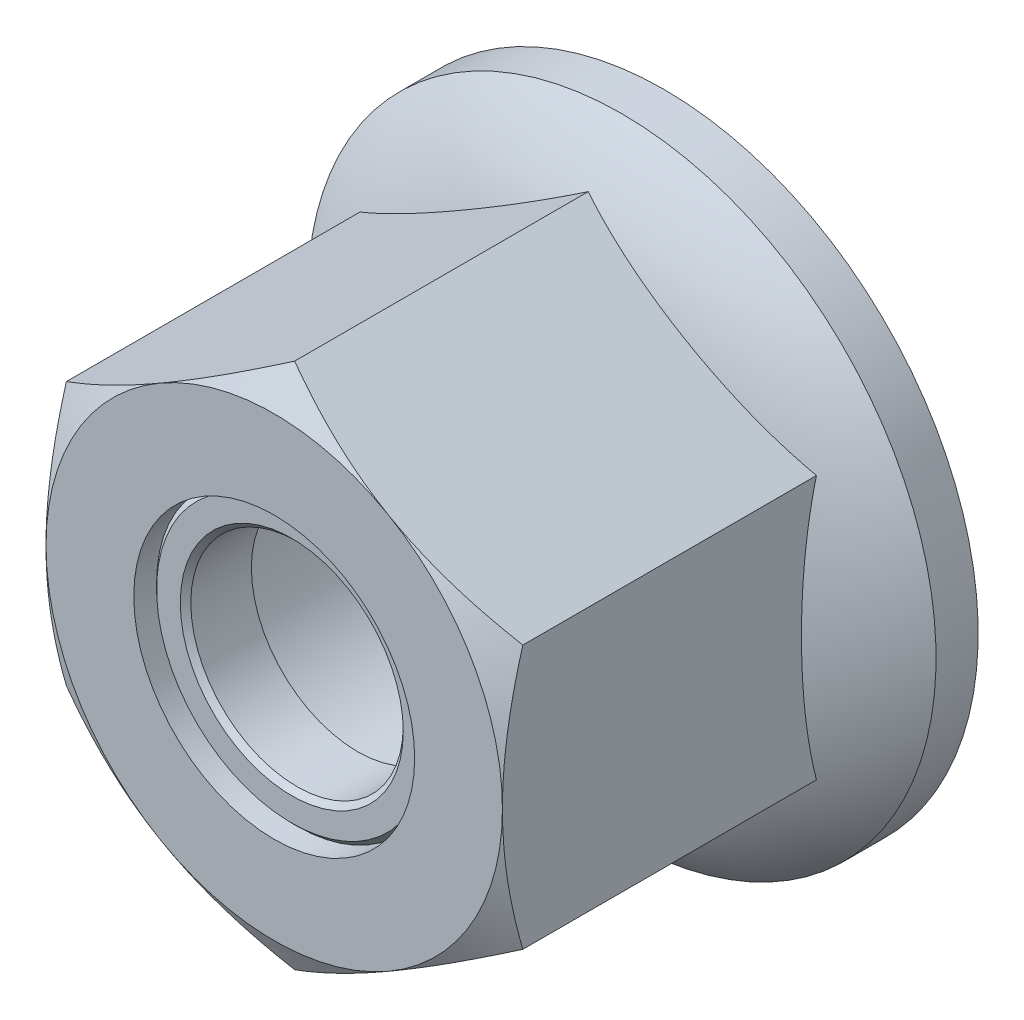
SolidWorks part; units mm, degrees
material "Alloy Steel"
ref_plane "Front Plane" through (0, 0, 0) normal (0, 0, 1) x (1, 0, 0)
ref_plane "Top Plane" through (0, 0, 0) normal (0, 1, 0) x (1, 0, 0)
ref_plane "Right Plane" through (0, 0, 0) normal (1, 0, 0) x (0, 0, -1)
sketch "Sketch1" plane through (0, 0, 0) normal (0, 0, 1) x (1, 0, 0)
  line L1 (0, 7.5056) -> (-6.5, 3.7528)
  line L2 (-6.5, 3.7528) -> (-6.5, -3.7528)
  line L3 (-6.5, -3.7528) -> (0, -7.5056)
  line L4 (0, -7.5056) -> (6.5, -3.7528)
  line L5 (6.5, -3.7528) -> (6.5, 3.7528)
  line L6 (6.5, 3.7528) -> (0, 7.5056)
  circle A0 centre (0, 0) radius 6.5 construction
  circle A1 centre (0, 0) radius 4
  dimension "Thread Size" = 8
  dimension "Hex" = 13
extrude "Extrude1" add sketch "Sketch1" against normal blind 11.1
sketch "Sketch2" plane through (0, 0, 0) normal (0, 0, 1) x (1, 0, 0)
  circle A0 centre (0, 0) radius 6.5 construction
  circle A1 centre (0, 0) radius 6.5
extrude "Cut-Extrude1" cut sketch "Sketch2" against normal through all draft 60 flip side to cut
sketch "Sketch3" plane through (0, 0, 0) normal (1, 0, 0) x (0, 0, -1)
  line L0 (11.1, 8.95) -> (11.1, 4)
  line L1 (11.1, 4) -> (8.1, 4)
  line L2 (11.1, 8.95) -> (9.9, 8.95)
  line L3 (0, 0) -> (11.1, 0) construction
  line L4 (0, -3.7528) -> (0, 3.7528) construction
  line L5 (11.1, -3.7528) -> (11.1, 3.7528) construction
  line L6 (11.1, 3.7528) -> (11.1, 7.5056) construction
  line L7 (11.1, -4) -> (11.1, 4) construction
  line L8 (8.1, 4) -> (8.1, 8.95) construction
  arc A0 (9.9, 8.95) -> (8.1, 4) centre (15.8062, 4) ccw
  dimension "Flange OD" = 17.9
  dimension "Flange Thickness" = 1.2
  dimension "D1" = 1.8
revolve "Revolve1" add sketch "Sketch3" angle 360 about L3
sketch "Sketch5" plane through (0, 0, 0) normal (0, 0, 1) x (1, 0, 0)
  circle A1 centre (0, 0) radius 4
  circle A2 centre (0, 0) radius 4 construction
curve "Helix/Spiral1" [suppressed] pitch 1.25 height 12.35 turns 9.88 parameters "pitch"=1.25
sketch "Sketch10" plane through (0, 0, 0) normal (0, 0, 1) x (1, 0, 0)
  circle A1 centre (0, 0) radius 4 construction
  circle A2 centre (0, 0) radius 3.0257
  circle A3 centre (0, 0) radius 3.0257
  circle A4 centre (0, 0) radius 4
  dimension "D1" = 0.9743
extrude "Boss-Extrude1" add sketch "Sketch10" against normal blind 1.875 from offset 0.5 separate body offset against normal yes
chamfer "Chamfer1" distance 0.15 angle 45 2 edges at (4, 0, -0.5) (3.0257, 0, -0.5)
sketch "Sketch6" [suppressed] plane through (0, 0, 0) normal (1, 0, 0) x (0, 0, -1)
  line L0 (-1.0938, 4) -> (0, 4)
  line L1 (-1.0938, 4) -> (-0.625, 3.1881)
  line L2 (-0.625, 3.1881) -> (-0.4688, 3.1881)
  line L3 (-0.4688, 3.1881) -> (0, 4)
  line L4 (-0.5469, 3.1881) -> (-0.5469, 4) construction
  line L5 (-0.8594, 3.5941) -> (-0.2344, 3.5941) construction
  dimension "D1" = 60
  dimension "D2" = 0.1562
  dimension "D3" = 0.625
  dimension "D4" = 0.8119
sweep "Sweep1" [suppressed] add profiles "Sketch6" path "Helix/Spiral1"
sketch "Sketch7" [suppressed] plane through (0, 0, -2.375) normal (0, 0, 1) x (1, 0, 0)
  circle A1 centre (0, 0) radius 4
  circle A2 centre (0, 0) radius 4
  dimension "D1" = 0
extrude "Cut-Extrude2" [suppressed] cut sketch "Sketch7" against normal through all draft 45 and the other way through all
sketch "Sketch8" [suppressed] plane through (0, 0, -11.1) normal (0, 0, -1) x (-1, 0, 0)
  circle A1 centre (0, 0) radius 4
  circle A2 centre (0, 0) radius 4
  dimension "D1" = 0
extrude "Cut-Extrude3" [suppressed] cut sketch "Sketch8" against normal through all draft 45 and the other way through all draft 45
ref_axis "Center Axis 1" [suppressed] through (0, 0, -14.0757) along (0, 0, 1)
ref_plane "Contact Plane 1" [suppressed] through (0, 0, -11.1) normal (0, 0, -1) x (-1, 0, 0)
equation "\"D3@Helix/Spiral1\" = \"pitch@Helix/Spiral1\"+\"Height@Extrude1\""
equation "\"D2@Sketch6\"=\"pitch@Helix/Spiral1\"*.125"
equation "\"D3@Sketch6\"=\"pitch@Helix/Spiral1\"*.50"
equation "\"D1@Sketch10\"=\"D4@Sketch6\"*1.2"
equation "\"D1@Boss-Extrude1\"=\"pitch@Helix/Spiral1\"*1.5"
equation "\"D1@Sketch3\"=\"Flange Thickness@Sketch3\"*1.5"
